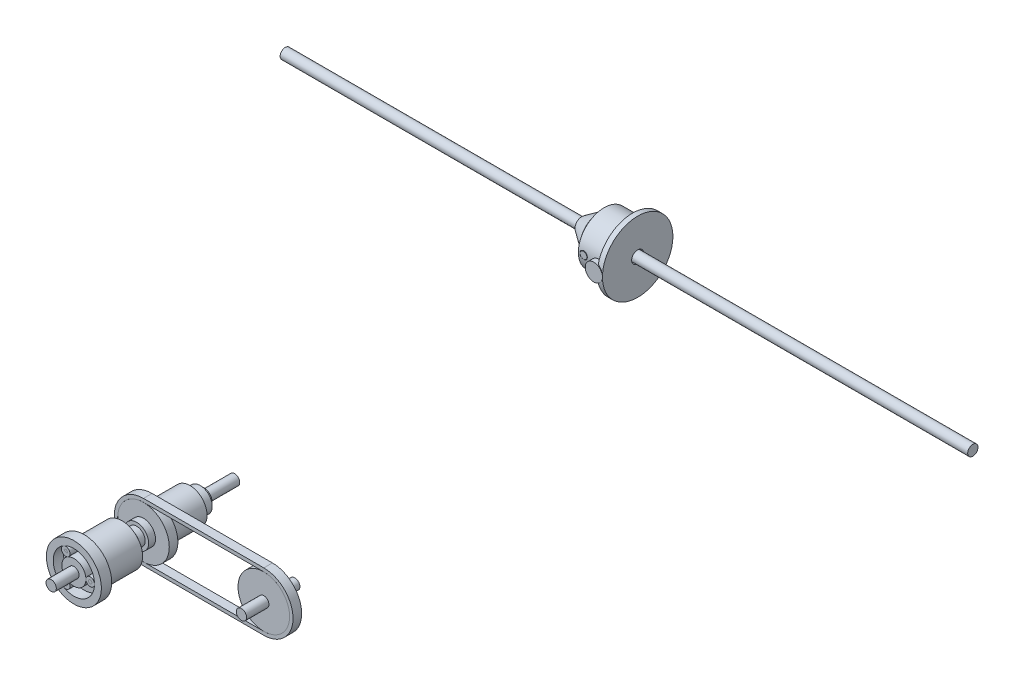
SolidWorks part; units mm, degrees
other "RD S Gear Inner"
other "RD S Gear Outer"
other "RD L Gear Left"
other "RD L Gear Right"
other "RD Ring Gear"
other "RD Pinion"
other "RD S Gear Inner"
other "Main Shaft"
ref_plane "Front Plane" through (0, 0, 0) normal (0, 0, 1) x (1, 0, 0)
ref_plane "Top Plane" through (0, 0, 0) normal (0, 1, 0) x (1, 0, 0)
ref_plane "Right Plane" through (0, 0, 0) normal (1, 0, 0) x (0, 0, -1)
sketch "Top View Layout" plane through (0, 0, 0) normal (0, 1, 0) x (1, 0, 0)
  line L0 (-100, 125) -> (100, 125)
  line L1 (0, 125) -> (0, -125)
  line L2 (-100, -125) -> (100, -125)
  line L3 (0, -15) -> (35, -15) construction
  line L4 (35, -15) -> (35, -125) construction
  line L5 (2.5, 114.75) -> (2.5, 135.25) construction
  line L6 (-2.5, 114.75) -> (2.5, 114.75) construction
  line L7 (-8.75, 127) -> (-2.75, 127) construction
  line L8 (-2.5, 114.75) -> (2.5, 114.75) construction
  line L9 (-2.5, 114.75) -> (-2.5, 116.25) construction
  line L10 (-2.5, 116.25) -> (2.5, 116.25) construction
  line L11 (2.5, 114.75) -> (2.5, 116.25) construction
  line L12 (2.5, 135.25) -> (1, 135.25) construction
  line L13 (2.5, 135.25) -> (2.5, 114.75) construction
  line L14 (2.5, 114.75) -> (1, 114.75) construction
  line L15 (1, 135.25) -> (1, 114.75) construction
  line L16 (-4.25, 128.5) -> (-2.75, 128.5) construction
  line L17 (-4.25, 128.5) -> (-4.25, 121.5) construction
  line L18 (-4.25, 121.5) -> (-2.75, 121.5) construction
  line L19 (-2.75, 128.5) -> (-2.75, 121.5) construction
  line L20 (-4.25, 128.5) -> (-2.75, 121.5) construction
  line L21 (-4.25, 121.5) -> (-2.75, 128.5) construction
  line L22 (-8.75, 128.5) -> (-7.25, 128.5) construction
  line L23 (-8.75, 128.5) -> (-8.75, 121.5) construction
  line L24 (-8.75, 121.5) -> (-7.25, 121.5) construction
  line L25 (-7.25, 128.5) -> (-7.25, 121.5) construction
  line L26 (-8.75, 128.5) -> (-7.25, 121.5) construction
  line L27 (-8.75, 121.5) -> (-7.25, 128.5) construction
  line L28 (-8.75, 123) -> (-2.75, 123) construction
  line L29 (-5.75, 123) -> (-5.75, 120.2863) construction
  line L30 (-5.75, 127) -> (-5.75, 129.2691) construction
  point P8 (0, 114.75)
  point P9 (0, 0)
  point P11 (2.5, 125)
  point P16 (2.5, 125)
  point P19 (0, 114.75)
  point P23 (-3.5, 125)
  point P28 (-8, 125)
  dimension "D1" = 250
  dimension "D2" = 200
  dimension "D3" = 35
  dimension "D4" = 15
  dimension "D5" = 5
  dimension "D6" = 20.5
  dimension "D7" = 1.5
  dimension "D8" = 1.5
  dimension "D9" = 1.5
  dimension "D10" = 7
  dimension "D11" = 3.5
  dimension "D12" = 8
  dimension "D13" = 1.5
  dimension "D14" = 1.5
ref_plane "Left" through (100, 0, 0) normal (-1, 0, 0) x (0, 0, 1)
ref_plane "Right" through (-100, 0, 0) normal (-1, 0, 0) x (0, 0, 1)
sketch "Left Wheels" plane through (100, 0, 0) normal (-1, 0, 0) x (0, 0, 1)
  circle A0 centre (125, 0) radius 25
  circle A1 centre (-125, 0) radius 25
  dimension "D1" = 50
  dimension "D2" = 50
sketch "Right Wheels" plane through (-100, 0, 0) normal (-1, 0, 0) x (0, 0, 1)
  circle A0 centre (-125, 0) radius 25 construction
  circle A1 centre (125, 0) radius 25 construction
  circle A2 centre (-125, 0) radius 25
  circle A3 centre (125, 0) radius 25
ref_plane "Rear Differential Pinion Plane" through (0, 0, -114.75) normal (0, 0, 1) x (1, 0, 0)
sketch "Rear Differential Pinion Profile" plane through (0, 0, -114.75) normal (0, 0, 1) x (1, 0, 0)
  circle A0 centre (0, 0) radius 2.5
ref_plane "Rear Differential Ring Gear Plane" through (2.5, 0, 0) normal (1, 0, 0) x (0, 0, -1)
ref_plane "Rear Axle" through (0, 0, -125) normal (0, 0, 1) x (1, 0, 0)
sketch "Rear Differential Ring Gear Profile" plane through (2.5, 0, 0) normal (1, 0, 0) x (0, 0, -1)
  line L0 (114.75, 0) -> (135.25, 0) construction
  circle A0 centre (125, 0) radius 10.25
extrude "Rear Differential Pinion" add sketch "Rear Differential Pinion Profile" against normal blind 1.5 contours A0
extrude "Rear Differential Ring Gear" add sketch "Rear Differential Ring Gear Profile" against normal blind 1.5 separate body contours A0
ref_plane "RD Inner L Gear Plane" through (-2.75, 0, 0) normal (1, 0, 0) x (0, 0, -1)
ref_plane "RD Outer L Gear Plane" through (-8.75, 0, 0) normal (1, 0, 0) x (0, 0, -1)
sketch "RD Inner L Gear Profile" plane through (-2.75, 0, 0) normal (1, 0, 0) x (0, 0, -1)
  circle A0 centre (125, 0) radius 3.5
sketch "RD Outer L Gear Profile" plane through (-8.75, 0, 0) normal (1, 0, 0) x (0, 0, -1)
  line L0 (128.5, 0) -> (121.5, 0) construction
  circle A0 centre (125, 0) radius 3.5
ref_plane "RD Inner S Gear Plane" through (0, 0, -121.5) normal (0, 0, 1) x (1, 0, 0)
ref_plane "RD Outer S Gear Plane" through (0, 0, -128.5) normal (0, 0, 1) x (1, 0, 0)
sketch "RD Inner S Gear Profile" plane through (0, 0, -121.5) normal (0, 0, 1) x (1, 0, 0)
  line L0 (-8.75, 0) -> (-7.25, 0) construction
  circle A0 centre (-5.75, 0) radius 3
sketch "RD Outer S Gear Profile" plane through (0, 0, -128.5) normal (0, 0, 1) x (1, 0, 0)
  line L0 (-8.75, 0) -> (-7.25, 0) construction
  circle A2 centre (-5.75, 0) radius 3
extrude "RD Outer L Gear Extrude" add sketch "RD Outer L Gear Profile" along normal blind 1.5 separate body contours A0
extrude "RD Inner L Gear Extrude" add sketch "RD Inner L Gear Profile" against normal blind 1.5 separate body contours A0
extrude "RD Outer S Gear Extrude" add sketch "RD Outer S Gear Profile" along normal blind 1.5 separate body contours A2
extrude "RD Inner S Gear Extrude" add sketch "RD Inner S Gear Profile" against normal blind 1.5 separate body contours A0
sketch "RD Ring Gear Case Profile" plane through (1, 0, 0) normal (-1, 0, 0) x (0, 0, 1)
  line L0 (-121.5, 3.2113) -> (-121.5, -3.2113)
  line L1 (-128.5, 3.2113) -> (-128.5, -3.2113)
  line L2 (-121.5, 6.6332) -> (-121.5, 3.2113) construction
  line L3 (-128.5, 6.6332) -> (-128.5, 3.2113) construction
  line L4 (-121.5, -3.2113) -> (-121.5, -6.6332) construction
  line L5 (-128.5, -3.2113) -> (-128.5, -6.6332) construction
  circle A0 centre (-125, 0) radius 7.5
  arc A1 (-121.5, 3.2113) -> (-128.5, 3.2113) centre (-125, 0) ccw
  arc A2 (-121.5, -3.2113) -> (-121.5, 3.2113) centre (-125, 0) ccw construction
  arc A3 (-128.5, 3.2113) -> (-128.5, -3.2113) centre (-125, 0) ccw construction
  arc A4 (-128.5, -3.2113) -> (-121.5, -3.2113) centre (-125, 0) ccw
  point P7 (-121.5, 0)
  dimension "D1" = 15
  dimension "D2" = 9.5
extrude "RD Ring Gear Case " add sketch "RD Ring Gear Case Profile" along normal blind 8.25
sketch "Sketch11" plane through (-7.25, 0, 0) normal (-1, 0, 0) x (0, 0, 1)
  circle A0 centre (-125, 0) radius 5.5
  circle A1 centre (-125, 0) radius 4.75
  arc A2 (-121.5, 3.2113) -> (-128.5, 3.2113) centre (-125, 0) ccw construction
  dimension "D1" = 11
extrude "Boss-Extrude8" add sketch "Sketch11" along normal up to vertex up to point (-8.75, 0, -128.5)
fillet "Fillet1" radius 2 1 edges at (-7.25, 0, -119.5)
sketch "Sketch12" plane through (0, 0, -125) normal (0, 0, 1) x (1, 0, 0)
  line L0 (-8.75, 0) -> (-13.75, 0) construction
  line L1 (-8.75, 0) -> (-7.25, 0) construction
  line L2 (-8.75, 0) -> (-7.25, 0) construction
  line L3 (-100, 0) -> (100, 0) construction
  line L4 (-100, 0) -> (100, 0) construction
  line L5 (-8.75, 5.5) -> (-8.75, -5.5) construction
  line L6 (-13.75, 0) -> (-13.75, 2)
  line L7 (-13.75, 2) -> (-8.75, 5.5)
  line L8 (-13.75, 0) -> (-8.75, 0)
  line L9 (-8.75, 0) -> (-8.75, 5.5)
  point P15 (-13.75, 1)
  dimension "D1" = 5
  dimension "D2" = 2
revolve "Revolve1" add sketch "Sketch12" angle 360 about L0
sketch "Sketch13" plane through (2.5, 0, 0) normal (1, 0, 0) x (0, 0, -1)
  circle A0 centre (125, 0) radius 1.75
  dimension "D1" = 3.5
extrude "Cut-Extrude1" cut sketch "Sketch13" against normal through all
sketch "Sketch14" plane through (0, 0, -121.5) normal (0, 0, 1) x (1, 0, 0)
  circle A0 centre (-5.75, 0) radius 1
  dimension "D1" = 2
extrude "Boss-Extrude9" add sketch "Sketch14" along normal blind 4
sketch "Sketch15" plane through (0, 0, -121.5) normal (0, 0, 1) x (1, 0, 0)
  circle A0 centre (-5.75, 0) radius 1.1
  dimension "D1" = 2.2
extrude "Cut-Extrude2" cut sketch "Sketch15" against normal through all both and the other way through all
extrude "Boss-Extrude10" add sketch "Sketch14<2>" against normal blind 4 from surface starting at face at (-2.75, 0, -128.5)
sketch "Sketch14<2>" plane through (0, 0, -121.5) normal (0, 0, 1) x (1, 0, 0) same geometry as "Sketch14"
sketch "Sketch16" plane through (-8.75, 0, 0) normal (-1, 0, 0) x (0, 0, 1)
  circle A0 centre (-125, 0) radius 1.5
  dimension "D1" = 3
extrude "Boss-Extrude11" add sketch "Sketch16" along normal up to vertex (91.25 mm away) up to point (-100, 0, -125)
sketch "Sketch17" plane through (-2.75, 0, 0) normal (1, 0, 0) x (0, 0, -1)
  circle A0 centre (125, 0) radius 1.5 construction
  circle A1 centre (125, 0) radius 1.5
extrude "Boss-Extrude12" add sketch "Sketch17" along normal up to vertex (102.75 mm away) up to point (100, 0, -125)
sketch "Transfer Case Layout" plane through (0, 0, 0) normal (0, 1, 0) x (1, 0, 0)
  line L0 (0, 125) -> (0, -125) construction
  line L1 (-7.5, -13.75) -> (7.5, -13.75)
  line L2 (-7.5, -13.75) -> (-7.5, -16.25)
  line L3 (-7.5, -16.25) -> (7.5, -16.25)
  line L4 (7.5, -13.75) -> (7.5, -16.25)
  line L5 (-7.5, -13.75) -> (7.5, -16.25) construction
  line L6 (-7.5, -16.25) -> (7.5, -13.75) construction
  line L7 (27.5, -13.75) -> (42.5, -13.75)
  line L8 (27.5, -13.75) -> (27.5, -16.25)
  line L9 (27.5, -16.25) -> (42.5, -16.25)
  line L10 (42.5, -13.75) -> (42.5, -16.25)
  line L11 (27.5, -13.75) -> (42.5, -16.25) construction
  line L12 (27.5, -16.25) -> (42.5, -13.75) construction
  line L13 (2.5, -17.25) -> (-2.5, -17.25)
  line L14 (2.5, -17.25) -> (2.5, -16.25)
  line L15 (2.5, -16.25) -> (-2.5, -16.25)
  line L16 (-2.5, -17.25) -> (-2.5, -16.25)
  line L17 (2.5, -17.25) -> (-2.5, -16.25) construction
  line L18 (2.5, -16.25) -> (-2.5, -17.25) construction
  line L19 (-2, -4.75) -> (-2, -10.75)
  line L20 (3.5, -18.25) -> (-3.5, -18.25)
  line L21 (3.5, -18.25) -> (3.5, -16.25)
  line L22 (3.5, -16.25) -> (-3.5, -16.25)
  line L23 (-3.5, -18.25) -> (-3.5, -16.25)
  line L24 (3.5, -18.25) -> (-3.5, -16.25) construction
  line L25 (3.5, -16.25) -> (-3.5, -18.25) construction
  line L26 (2.5, -20) -> (-2.5, -20)
  line L27 (2.5, -20) -> (2.5, -17.5)
  line L28 (2.5, -17.5) -> (-2.5, -17.5)
  line L29 (-2.5, -20) -> (-2.5, -17.5)
  line L30 (2.5, -20) -> (-2.5, -17.5) construction
  line L31 (2.5, -17.5) -> (-2.5, -20) construction
  line L32 (-3.5, -9.25) -> (3.5, -9.25)
  line L33 (-3.5, -9.25) -> (-3.5, -10.75)
  line L34 (-3.5, -10.75) -> (3.5, -10.75)
  line L35 (3.5, -9.25) -> (3.5, -10.75)
  line L36 (-3.5, -9.25) -> (3.5, -10.75) construction
  line L37 (-3.5, -10.75) -> (3.5, -9.25) construction
  line L38 (-3.5, -4.75) -> (3.5, -4.75)
  line L39 (-3.5, -4.75) -> (-3.5, -6.25)
  line L40 (-3.5, -6.25) -> (3.5, -6.25)
  line L41 (3.5, -4.75) -> (3.5, -6.25)
  line L42 (-3.5, -4.75) -> (3.5, -6.25) construction
  line L43 (-3.5, -6.25) -> (3.5, -4.75) construction
  line L44 (2, -4.75) -> (2, -10.75)
  line L45 (0, -6.25) -> (0, -9.25) construction
  line L46 (-5, -2.75) -> (5, -2.75) construction
  line L47 (-5, -2.75) -> (-5, -12.75) construction
  line L48 (-5, -12.75) -> (5, -12.75) construction
  line L49 (5, -2.75) -> (5, -12.75) construction
  line L50 (-5, -2.75) -> (5, -12.75) construction
  line L51 (-5, -12.75) -> (5, -2.75) construction
  line L52 (-6, -22.5) -> (-6, -24)
  line L53 (-2.5, -1.75) -> (2.5, -1.75)
  line L54 (-2.5, -1.75) -> (-2.5, -2.75)
  line L55 (-2.5, -2.75) -> (2.5, -2.75)
  line L56 (2.5, -1.75) -> (2.5, -2.75)
  line L57 (-2.5, -1.75) -> (2.5, -2.75) construction
  line L58 (-2.5, -2.75) -> (2.5, -1.75) construction
  line L59 (-2.5, 1.25) -> (2.5, 1.25)
  line L60 (-2.5, 1.25) -> (-2.5, -0.75)
  line L61 (-2.5, -0.75) -> (2.5, -0.75)
  line L62 (2.5, 1.25) -> (2.5, -0.75)
  line L63 (-2.5, 1.25) -> (2.5, -0.75) construction
  line L64 (-2.5, -0.75) -> (2.5, 1.25) construction
  line L65 (3.5, 0.25) -> (-3.5, 0.25)
  line L66 (3.5, 0.25) -> (3.5, -2.25)
  line L67 (3.5, -2.25) -> (-3.5, -2.25)
  line L68 (-3.5, 0.25) -> (-3.5, -2.25)
  line L69 (3.5, 0.25) -> (-3.5, -2.25) construction
  line L70 (3.5, -2.25) -> (-3.5, 0.25) construction
  line L71 (-2.5, -22.5) -> (2.5, -22.5)
  line L72 (-2.5, -22.5) -> (-2.5, -27.5)
  line L73 (-2.5, -27.5) -> (2.5, -27.5)
  line L74 (2.5, -22.5) -> (2.5, -27.5)
  line L75 (-2.5, -22.5) -> (2.5, -27.5) construction
  line L76 (-2.5, -27.5) -> (2.5, -22.5) construction
  line L77 (-6, -24) -> (6, -24)
  line L78 (6, -24) -> (6, -22.5)
  line L79 (6, -22.5) -> (-6, -22.5)
  line L80 (-4.5, -22.5) -> (-4.5, -24)
  line L81 (4.5, -22.5) -> (4.5, -24)
  line L82 (-6, -24) -> (-6, -33.5) construction
  line L83 (2.5, -29.5) -> (-2.5, -29.5)
  line L84 (2.5, -29.5) -> (2.5, -28)
  line L85 (2.5, -28) -> (-2.5, -28)
  line L86 (-2.5, -29.5) -> (-2.5, -28)
  line L87 (2.5, -29.5) -> (-2.5, -28) construction
  line L88 (2.5, -28) -> (-2.5, -29.5) construction
  line L89 (-4.5, -26.5) -> (4.5, -26.5)
  line L90 (-4.5, -26.5) -> (-4.5, -29.5)
  line L91 (-4.5, -29.5) -> (4.5, -29.5)
  line L92 (4.5, -26.5) -> (4.5, -29.5)
  line L93 (-4.5, -26.5) -> (4.5, -29.5) construction
  line L94 (-4.5, -29.5) -> (4.5, -26.5) construction
  line L95 (6, -24) -> (6, -33.5) construction
  line L96 (-3.5, -33.5) -> (-3.5, -36.5)
  line L97 (6, -36.5) -> (-6, -36.5)
  line L98 (6, -36.5) -> (6, -33.5)
  line L99 (6, -33.5) -> (-6, -33.5)
  line L100 (-6, -36.5) -> (-6, -33.5)
  line L101 (6, -36.5) -> (-6, -33.5) construction
  line L102 (6, -33.5) -> (-6, -36.5) construction
  line L103 (3.5, -33.5) -> (3.5, -36.5)
  line L104 (0, -28) -> (0, -43.1129)
  line L109 (8, -36.5) -> (-8, -36.5)
  line L110 (8, -36.5) -> (8, -33.5)
  line L111 (8, -33.5) -> (-8, -33.5)
  line L112 (-8, -36.5) -> (-8, -33.5)
  line L113 (8, -36.5) -> (-8, -33.5) construction
  line L114 (8, -33.5) -> (-8, -36.5) construction
  line L115 (0, -27.5) -> (0, -9.25)
  line L116 (0, -6.25) -> (0, -1.75)
  line L117 (0, -0.75) -> (0, 11.0375)
  line L118 (35, -22.7597) -> (35, -7.2403)
  point P0 (0, -15)
  point P6 (35, -15)
  point P12 (0, -16.75)
  point P19 (0, -17.25)
  point P24 (0, -18.75)
  point P29 (0, -10)
  point P34 (0, -5.5)
  point P43 (0, -7.75)
  point P50 (0, -2.25)
  point P55 (0, 0.25)
  point P60 (0, -1)
  point P65 (0, -25)
  point P72 (0, -22.5)
  point P79 (0, -28.75)
  point P84 (0, -28)
  point P92 (0, -35)
  point P98 (0, -35)
  point P99 (0, -35)
  point P110 (0, 0)
  point P113 (35, -15)
  point P114 (0, 0)
  dimension "D1" = 2.5
  dimension "D2" = 2.5
  dimension "D3" = 15
  dimension "D4" = 15
  dimension "D5" = 1
  dimension "D6" = 5
  dimension "D7" = 7
  dimension "D8" = 2
  dimension "D9" = 0.25
  dimension "D10" = 2.5
  dimension "D11" = 7
  dimension "D12" = 5
  dimension "D13" = 1.5
  dimension "D14" = 1.5
  dimension "D15" = 1.5
  dimension "D16" = 1.5
  dimension "D17" = 6
  dimension "D18" = 2
  dimension "D19" = 1.5
  dimension "D20" = 5
  dimension "D21" = 1
  dimension "D22" = 2
  dimension "D23" = 1
  dimension "D24" = 7
  dimension "D25" = 2.5
  dimension "D26" = 0.5
  dimension "D27" = 5
  dimension "D28" = 5
  dimension "D29" = 10
  dimension "D30" = 1.5
  dimension "D31" = 12
  dimension "D32" = 1.5
  dimension "D33" = 1.5
  dimension "D34" = 1.5
  dimension "D35" = 0.5
  dimension "D36" = 3
  dimension "D37" = 3
  dimension "D38" = 20
  dimension "D39" = 2.5
  dimension "D40" = 2.5
  dimension "D41" = 7
  dimension "D42" = 2
  dimension "D43" = 16
ref_plane "FWD Sprocket Plane" through (0, 0, 15) normal (0, 0, 1) x (1, 0, 0)
sketch "Sketch19" plane through (0, 0, 15) normal (0, 0, 1) x (1, 0, 0)
  circle A0 centre (35, 0) radius 7.5
  circle A1 centre (0, 0) radius 7.5
  point P6 (7.5, 0)
  point P9 (27.5, 0)
extrude "FWD Sprockets" add sketch "Sketch19" along normal up to vertex (1.25 mm away) and the other way up to vertex (1.25 mm away) separate body up to point (-7.5, 0, 16.25) other way up to point (-7.5, 0, 13.75)
sketch "Sketch20" plane through (0, 0, 15) normal (0, 0, 1) x (1, 0, 0)
  line L0 (0, 8.5) -> (35, 8.5)
  line L1 (0, -8.5) -> (35, -8.5)
  line L2 (0, 7.5) -> (35, 7.5)
  line L3 (0, -7.5) -> (35, -7.5)
  circle A0 centre (0, 0) radius 7.5 construction
  arc A1 (0, 7.5) -> (0, -7.5) centre (0, 0) ccw
  circle A2 centre (35, 0) radius 7.5 construction
  arc A3 (35, -7.5) -> (35, 7.5) centre (35, 0) ccw
  arc A4 (0, 8.5) -> (0, -8.5) centre (0, 0) ccw
  arc A5 (35, -8.5) -> (35, 8.5) centre (35, 0) ccw
  arc A6 (4, -7.5) -> (4, 7.5) centre (0, 0) ccw construction
  arc A7 (0, -7.5) -> (0, 7.5) centre (0, 0) ccw construction
  arc A8 (35, 7.5) -> (35, -7.5) centre (35, 0) ccw construction
  arc A9 (31, 7.5) -> (31, -7.5) centre (35, 0) ccw construction
  arc A10 (4, 7.5) -> (0, 8.5) centre (0, 0) ccw construction
  arc A11 (35, 8.5) -> (31, 7.5) centre (35, 0) ccw construction
  arc A12 (31, -7.5) -> (35, -8.5) centre (35, 0) ccw construction
  arc A13 (0, -8.5) -> (4, -7.5) centre (0, 0) ccw construction
  dimension "D1" = 1
  dimension "D2" = 1
extrude "FWD Sprocket Chain" add sketch "Sketch20" along normal up to surface and the other way up to surface separate body up to face at (7.5, 0, 16.25) other way up to face at (7.5, 0, 13.75)
sketch "Sketch21" plane through (0, 0, 16.25) normal (0, 0, 1) x (1, 0, 0)
  circle A0 centre (0, 0) radius 2.5
  point P3 (2.5, 0)
extrude "FWD Sprocket Dog Gear" add sketch "Sketch21" along normal up to vertex (1 mm away) up to point (-2.5, 0, 17.25)
ref_plane "Mode Sleeve Gear Plane" through (0, 0, 18.25) normal (0, 0, 1) x (1, 0, 0)
sketch "Sketch22" plane through (0, 0, 18.25) normal (0, 0, 1) x (1, 0, 0)
  circle A0 centre (0, 0) radius 3.5
  circle A1 centre (0, 0) radius 2.5 construction
  circle A2 centre (0, 0) radius 2.5
extrude "Mode Sleeve Gear" add sketch "Sketch22" against normal up to vertex (2 mm away) separate body up to point (3.5, 0, 16.25)
sketch "Sketch23" plane through (0, 0, 18.25) normal (0, 0, 1) x (1, 0, 0)
  circle A0 centre (0, 0) radius 2.5 construction
  circle A1 centre (0, 0) radius 2.5
extrude "Mode Sleeve Main Shaft Gear" add sketch "Sketch23" along normal up to vertex (1.75 mm away) and the other way up to vertex (0.75 mm away) separate body up to point (2.5, 0, 20) other way up to point (2.5, 0, 17.5)
ref_plane "Range Sleeve Rear Plane" through (0, 0, 22.5) normal (0, 0, 1) x (1, 0, 0)
sketch "Sketch24" plane through (0, 0, 22.5) normal (0, 0, 1) x (1, 0, 0)
  circle A0 centre (0, 0) radius 2.5
extrude "Main Shaft Range Sleeve Gear" add sketch "Sketch24" along normal up to vertex (5 mm away) separate body up to point (-2.5, 0, 27.5)
sketch "Sketch25" plane through (0, 0, 22.5) normal (0, 0, 1) x (1, 0, 0)
  circle A0 centre (0, 0) radius 6
  circle A3 centre (0, 0) radius 4.5
extrude "Carrier Range Sleeve Gear" add sketch "Sketch25" along normal up to vertex (1.5 mm away) separate body up to point (6, 0, 24)
ref_plane "Range Sleeve Input Shaft Side" through (0, 0, 29.5) normal (0, 0, 1) x (1, 0, 0)
sketch "Sketch27" plane through (0, 0, 29.5) normal (0, 0, 1) x (1, 0, 0)
  circle A0 centre (0, 0) radius 2.5
extrude "Input Range Sleeve Gear" add sketch "Sketch27" against normal up to vertex (1.5 mm away) separate body up to point (2.5, 0, 28)
sketch "Sketch28" plane through (0, 0, 29.5) normal (0, 0, 1) x (1, 0, 0)
  circle A0 centre (0, 0) radius 4.5
  circle A1 centre (0, 0) radius 2.5 construction
  circle A2 centre (0, 0) radius 2.5
extrude "Range Sleeve Sleeve Gear" add sketch "Sketch28" against normal up to vertex (3 mm away) separate body up to point (4.5, 0, 26.5)
ref_plane "Planetary Input Side Plane" through (0, 0, 36.5) normal (0, 0, 1) x (1, 0, 0)
sketch "Sketch29" plane through (0, 0, 36.5) normal (0, 0, 1) x (1, 0, 0)
  circle A0 centre (0, 0) radius 3.5
extrude "Planetary Sun Gear" add sketch "Sketch29" against normal up to vertex (3 mm away) separate body up to point (3.5, 0, 33.5)
sketch "Sketch30" plane through (0, 0, 36.5) normal (0, 0, 1) x (1, 0, 0)
  line L0 (6, 0) -> (-6, 0) construction
  circle A0 centre (4.75, 0) radius 1.25
extrude "Planetary Planet Gear" add sketch "Sketch30" against normal up to vertex (3 mm away) separate body up to point (6, 0, 33.5)
pattern_circular "Planetary Planet Gear x 3" count 3 over 360 about axis through (0, 0, 28) along (0, 0, 1) reverse direction yes of bodies 132
sketch "Sketch31" plane through (0, 0, 36.5) normal (0, 0, 1) x (1, 0, 0)
  circle A0 centre (0, 0) radius 6
  circle A1 centre (0, 0) radius 8
extrude "Planetary Ring Gear" add sketch "Sketch31" against normal up to vertex (3 mm away) separate body up to point (8, 0, 33.5)
ref_plane "Planetary Rear Side Plane" through (0, 0, 33.5) normal (0, 0, 1) x (1, 0, 0)
sketch "Sketch32" plane through (0, 0, 33.5) normal (0, 0, 1) x (1, 0, 0)
  line L0 (3.5, 0) -> (6, 0) construction
  line L1 (0, 0) -> (4.75, 0) construction
  line L2 (0, 0) -> (-2.375, -4.1136) construction
  circle A0 centre (0, 0) radius 6
  circle A1 centre (4.75, 0) radius 0.5
  circle A2 centre (-2.375, -4.1136) radius 0.5
  circle A3 centre (-2.375, 4.1136) radius 0.5
  point P4 (4.75, 0)
  dimension "D1" = 1
  dimension "D3" = 120
  dimension "D4" = 4.75
  dimension "D2" = 3
extrude "Carrier" add sketch "Sketch32" against normal blind 1 separate body contours A3 | A0 A3 A2 A1 | A1 | A2 region at (0, 0, 33.5) region at (4.75, 0, 33.5) region at (-2.375, -4.1136, 33.5) region at (-2.375, 4.1136, 33.5)
extrude "Carrier Shafts" add sketch "Sketch32<3>" along normal up to vertex (3 mm away) contours A1 | A2 | A3 region at (4.75, 0, 33.5) region at (-2.375, -4.1136, 33.5) up to point (-3.5, 0, 36.5)
sketch "Sketch32<3>" plane through (0, 0, 33.5) normal (0, 0, 1) x (1, 0, 0) same geometry as "Sketch32"
sketch "Sketch33" plane through (0, 0, 33.5) normal (0, 0, 1) x (1, 0, 0)
  circle A0 centre (0, 0) radius 6 construction
  circle A1 centre (0, 0) radius 6
  circle A2 centre (0, 0) radius 5.5
  dimension "D1" = 0.5
extrude "Carrier Range Sleeve Gear Connect" add sketch "Sketch33" against normal up to surface (9.5 mm away) up to face at (6, 0, 24)
ref_plane "Center Diff Main Shaft Sidegear Plane" through (0, 0, 10.75) normal (0, 0, 1) x (1, 0, 0)
sketch "Sketch34" plane through (0, 0, 10.75) normal (0, 0, 1) x (1, 0, 0)
  circle A0 centre (0, 0) radius 3.5
extrude "Center Diff Main Shaft Side Gear" add sketch "Sketch34" against normal up to vertex (1.5 mm away) separate body up to point (3.5, 0, 9.25)
ref_plane "Center Diff Rear Shaft Sidegear Plane" through (0, 0, 4.75) normal (0, 0, 1) x (1, 0, 0)
ref_plane "Center Diff Mid Plane" through (0, 0, 7.75) normal (0, 0, 1) x (1, 0, 0)
mirror "Center Diff Rear Shaft Side Gear" about plane through (0, 0, 7.75) normal (0, 0, 1) of bodies 139
ref_plane "Center Diff Right Pinion Inner Plane" through (-2, 0, 0) normal (-1, 0, 0) x (0, 0, 1)
sketch "Sketch35" plane through (-2, 0, 0) normal (-1, 0, 0) x (0, 0, 1)
  line L0 (4.75, 0) -> (10.75, 0) construction
  circle A0 centre (7.75, 0) radius 3
extrude "Center Diff Right Pinion" add sketch "Sketch35" along normal up to vertex (1.5 mm away) separate body up to point (-3.5, 0, 10.75)
ref_plane "Center Diff Left Side Pinion Inner Plane" through (2, 0, 0) normal (-1, 0, 0) x (0, 0, 1)
sketch "Sketch36" plane through (2, 0, 0) normal (-1, 0, 0) x (0, 0, 1)
  line L0 (4.75, 0) -> (10.75, 0) construction
  circle A0 centre (7.75, 0) radius 3
extrude "Center Diff Left Pinion" add sketch "Sketch36" against normal up to vertex (1.5 mm away) separate body up to point (3.5, 0, 4.75)
ref_plane "Center Diff Rear Shaft Side Plane" through (0, 0, 2.75) normal (0, 0, 1) x (1, 0, 0)
sketch "Sketch37" plane through (0, 0, 2.75) normal (0, 0, 1) x (1, 0, 0)
  circle A0 centre (0, 0) radius 5
extrude "Center Diff Rear Axle Side Plate" add sketch "Sketch37" along normal up to vertex (2 mm away) separate body up to point (3.5, 0, 4.75)
mirror "Center Diff Main Shaft Side Plate" about plane through (0, 0, 7.75) normal (0, 0, 1) of bodies 143
sketch "Sketch38" plane through (0, 0, 2.75) normal (0, 0, 1) x (1, 0, 0)
  line L0 (3.5, -2.8284) -> (3.5, 2.8284)
  line L1 (-3.4263, -2.9173) -> (-3.5, -2.8284)
  line L2 (-3.5, -2.8284) -> (-3.5, 2.8284)
  circle A0 centre (0, 0) radius 5 construction
  circle A1 centre (0, 0) radius 5
  arc A2 (3.5, 2.8284) -> (-3.5, 2.8284) centre (0, 0) ccw
  arc A3 (3.5, -2.8284) -> (3.5, 2.8284) centre (0, 0) ccw construction
  arc A4 (-3.5, 2.8284) -> (-3.5, -2.8284) centre (0, 0) ccw construction
  arc A5 (-3.5, -2.8284) -> (3.5, -2.8284) centre (0, 0) ccw
  dimension "D1" = 0.5
extrude "Center Diff Case" add sketch "Sketch38" along normal up to surface (8 mm away) contours A1 A5 L2 A2 L0 region at (-4.8586, 0, 2.75) up to face at (5, 0, 10.75)
sketch "Sketch39" plane through (0, 0, 2.75) normal (0, 0, 1) x (1, 0, 0)
  circle A0 centre (0, 0) radius 2.5
extrude "Center Diff Lock Gear" add sketch "Sketch39" against normal up to vertex (1 mm away) up to point (2.5, 0, 1.75)
ref_plane "Lock Sleeve Plane" through (0, 0, -0.25) normal (0, 0, 1) x (1, 0, 0)
sketch "Sketch41" plane through (0, 0, -0.25) normal (0, 0, 1) x (1, 0, 0)
  circle A0 centre (0, 0) radius 3.5
  circle A1 centre (0, 0) radius 2.5 construction
  circle A2 centre (0, 0) radius 2.5
extrude "Lock Sleeve" add sketch "Sketch41" along normal up to vertex (2.5 mm away) separate body up to point (-3.5, 0, 2.25)
sketch "Sketch42" plane through (0, 0, -0.25) normal (0, 0, 1) x (1, 0, 0)
  circle A0 centre (0, 0) radius 2.5 construction
  circle A1 centre (0, 0) radius 2.5
extrude "Lock Sleeve Rear Shaft Gear" add sketch "Sketch42" along normal up to vertex (1 mm away) and the other way up to vertex (1 mm away) separate body up to point (2.5, 0, 0.75) other way up to point (2.5, 0, -1.25)
sketch "Sketch43" plane through (-2, 0, 0) normal (-1, 0, 0) x (0, 0, 1)
  line L0 (4.75, 0) -> (10.75, 0) construction
  circle A0 centre (7.75, 0) radius 0.5
  dimension "D1" = 1
extrude "Center Diff Pinion Rotation Point Cut" cut sketch "Sketch43" against normal through all both and the other way through all
sketch "Sketch45" plane through (0, 0, 2.75) normal (0, 0, 1) x (1, 0, 0)
  circle A0 centre (0, 0) radius 0.5
  dimension "D1" = 1
extrude "Center Diff Side Gear Rotation Point" cut sketch "Sketch45" against normal through all both and the other way through all
sketch "Sketch46" plane through (0, 0, -0.25) normal (0, 0, 1) x (1, 0, 0)
  circle A0 centre (0, 0) radius 1.5
  dimension "D1" = 3
extrude "Rear Shaft" add sketch "Sketch46" along normal up to vertex (1 mm away) and the other way blind 10 up to point (0, 0, 0.75)
sketch "Sketch47" plane through (0, 0, 2.75) normal (0, 0, 1) x (1, 0, 0)
  circle A0 centre (0, 0) radius 0.5
  dimension "D1" = 1
extrude "Center Diff Rear Shaft Side Axle" add sketch "Sketch47" along normal up to vertex (3.5 mm away) and the other way up to vertex (1 mm away) up to point (0, 0, 6.25) other way up to point (0, 0, 1.75)
sketch "Sketch48" plane through (-2, 0, 0) normal (-1, 0, 0) x (0, 0, 1)
  circle A0 centre (7.75, 0) radius 0.5 construction
  circle A1 centre (7.75, 0) radius 0.5
extrude "Center Diff Right Side Pinion Axle" add sketch "Sketch48" along normal up to vertex (3 mm away) up to point (-5, 0, 12.75)
sketch "Sketch49" plane through (2, 0, 0) normal (-1, 0, 0) x (0, 0, 1)
  circle A0 centre (7.75, 0) radius 0.5 construction
  circle A1 centre (7.75, 0) radius 0.5
extrude "Center Diff Left Side Pinion Axle" add sketch "Sketch49" against normal up to vertex (3 mm away) up to point (5, 0, 2.75)
sketch "Sketch50" plane through (0, 0, 18.25) normal (0, 0, 1) x (1, 0, 0)
  circle A0 centre (0, 0) radius 0.5
  dimension "D1" = 1
extrude "Main Shaft Sprocket Rotation Point Cut" cut sketch "Sketch50" against normal through all both and the other way through all
extrude "Main Shaft Extrude" add sketch "Sketch50<2>" against normal up to vertex (9 mm away) and the other way up to vertex (9.25 mm away) up to point (0, 0, 9.25) other way up to point (0, 0, 27.5)
sketch "Sketch50<2>" plane through (0, 0, 18.25) normal (0, 0, 1) x (1, 0, 0) same geometry as "Sketch50"
sketch "Sketch52" plane through (0, 0, 36.5) normal (0, 0, 1) x (1, 0, 0)
  circle A0 centre (0, 0) radius 1.5
  dimension "D1" = 3
extrude "Input Shaft Carrier Cut" cut sketch "Sketch52" against normal through all both and the other way through all
extrude "Input Shaft" add sketch "Sketch52<2>" along normal up to vertex (6.6129 mm away) and the other way up to vertex (8.5 mm away) up to point (0, 0, 43.1129) other way up to point (0, 0, 28)
sketch "Sketch52<2>" plane through (0, 0, 36.5) normal (0, 0, 1) x (1, 0, 0) same geometry as "Sketch52"
sketch "Sketch54" plane through (0, 0, 15) normal (0, 0, 1) x (1, 0, 0)
  circle A0 centre (35, 0) radius 1.5
  dimension "D1" = 3
extrude "FW Shaft" add sketch "Sketch54" along normal up to vertex (7.7597 mm away) and the other way up to vertex (7.7597 mm away) up to point (35, 0, 22.7597) other way up to point (35, 0, 7.2403)
